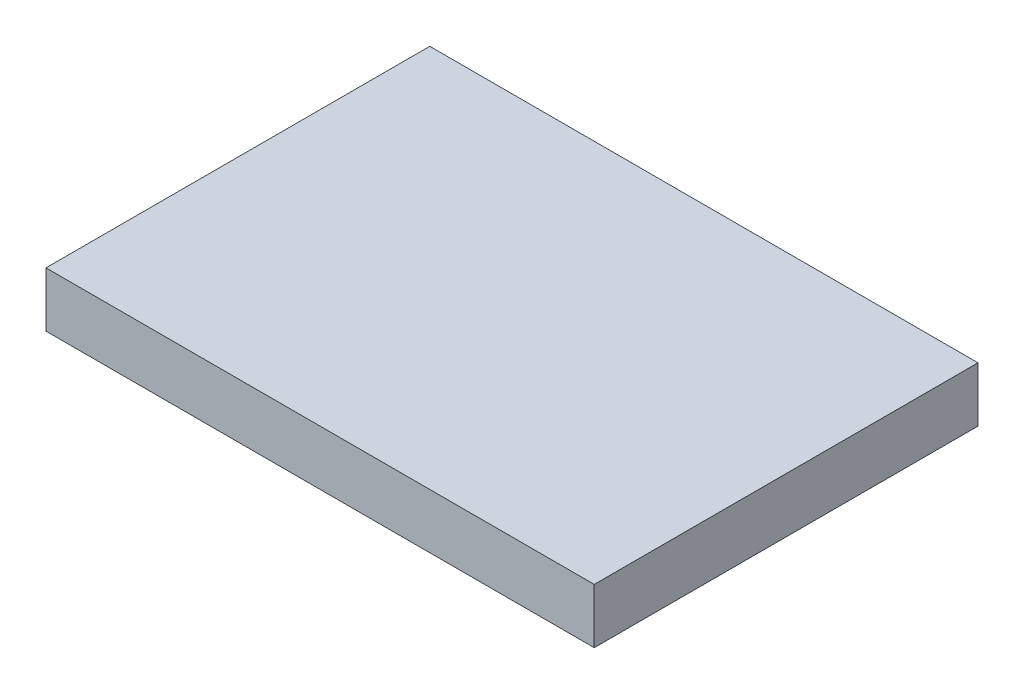
SolidWorks part; units mm, degrees
ref_plane "Front Plane" through (0, 0, 0) normal (0, 0, 1) x (1, 0, 0)
ref_plane "Top Plane" through (0, 0, 0) normal (0, 1, 0) x (1, 0, 0)
ref_plane "Right Plane" through (0, 0, 0) normal (1, 0, 0) x (0, 0, -1)
sketch "Sketch1" plane through (0, 0, 0) normal (0, 1, 0) x (1, 0, 0)
  line L1 (-150, -105) -> (150, -105)
  line L2 (-150, -105) -> (-150, 105)
  line L3 (-150, 105) -> (150, 105)
  line L4 (150, -105) -> (150, 105)
  line L5 (-150, -105) -> (150, 105) construction
  line L6 (-150, 105) -> (150, -105) construction
  point P0 (0, 0)
  dimension "D1" = 300
  dimension "D2" = 210
extrude "Boss-Extrude1" add sketch "Sketch1" along normal mid plane 30
